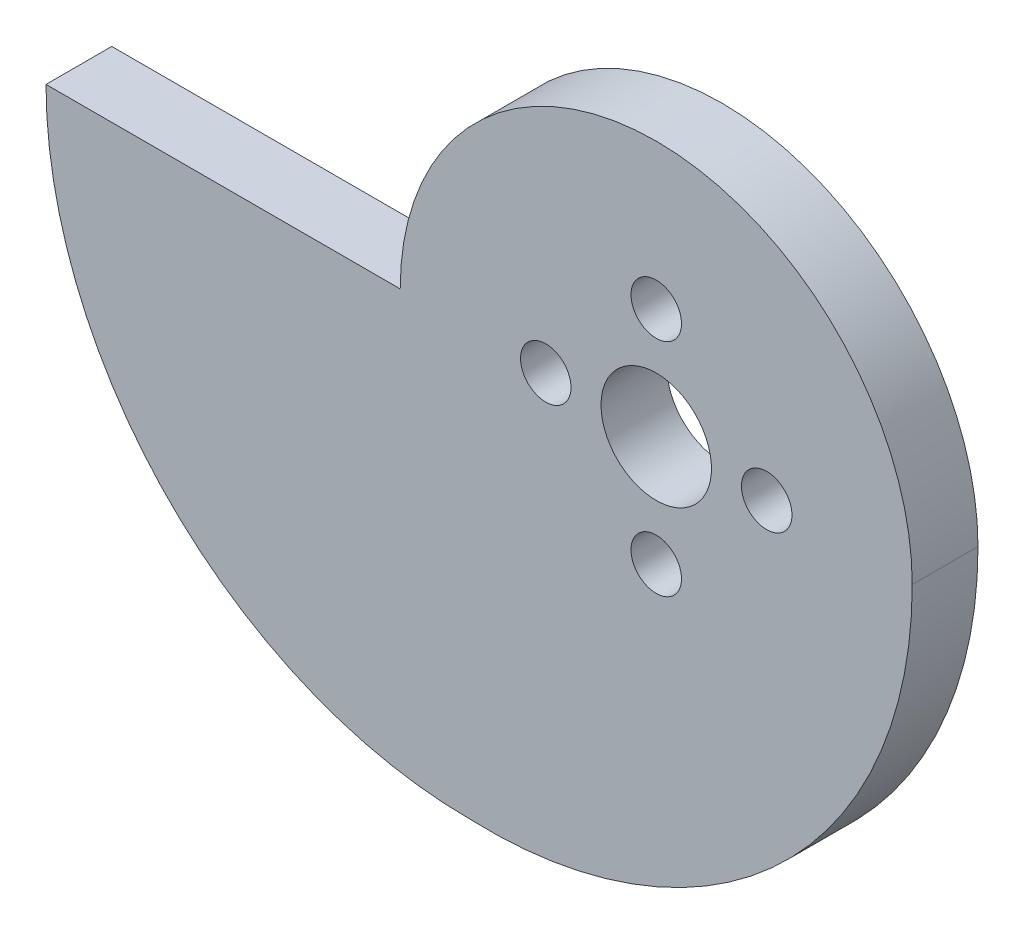
SolidWorks part; units mm, degrees
material "6061-T6 (SS)"
ref_plane "Front" through (0, 0, 0) normal (0, 0, 1) x (1, 0, 0)
ref_plane "Top" through (0, 0, 0) normal (0, 1, 0) x (1, 0, 0)
ref_plane "Right" through (0, 0, 0) normal (1, 0, 0) x (0, 0, -1)
ref_axis "side-side" through (80.9, 0, 0) along (-1, 0, 0)
ref_axis "up-down" through (0, 50, 0) along (0, -1, 0)
ref_axis "front-back" through (0, 0, -80.9) along (0, 0, 1)
sketch3d "3DSketch1"
  circle A4 centre (-8, 0, -7.9375) radius 1.2802
  circle A5 centre (0, -8, -7.9375) radius 1.2802
  circle A6 centre (0, 8, -7.9375) radius 1.2802
  circle A7 centre (8, 0, -7.9375) radius 1.2802
  circle A9 centre (0, 0, 2.5) radius 4
  point P13 (-8, 0, -6.6573)
  point P15 (0, -8, -6.6573)
  point P17 (0, 8, -6.6573)
  point P19 (8, 0, -6.6573)
  point P24 (0, 0, -1.5)
sketch "Sketch1" plane through (0, 0, 0) normal (0, 0, 1) x (1, 0, 0)
  line L0 (-13.462, -30.734) -> (18.542, -30.734) construction
  line L1 (18.542, 17.6106) -> (18.542, -21.2159) construction
  line L2 (50, 0) -> (-50, 0) construction
  line L3 (-44.196, 0) -> (-18.542, 0)
  arc A0 (-18.542, 0) -> (18.542, 0) centre (0, 0) cw
  arc A1 (-44.196, 0) -> (-13.462, -30.734) centre (-13.462, 0) ccw
  arc A2 (18.542, 0) -> (-13.462, -30.734) centre (-12.2172, 0) cw
  circle A3 centre (0, 0) radius 4 construction
  circle A4 centre (0, 0) radius 4
  dimension "D1" = 37.084
  dimension "D2" = 30.734
  dimension "D3" = 62.738
extrude "Boss-Extrude1" add sketch "Sketch1" along normal blind 4.7625
hole_wizard "#6 Clearance Hole1" positions "Sketch2" profile "Sketch3" hole size "#6" standard "ANSI Inch" end condition through all
sketch "Sketch2" plane through (0, 0, 4.7625) normal (0, 0, 1) x (1, 0, 0)
  point P0 (0, 8)
  point P3 (8, 0)
  point P6 (0, -8)
  point P9 (-8, 0)
sketch "Sketch3" plane through (0, 8, 4.7625) normal (1, 0, 0) x (0, -1, 0)
  line L0 (0, 0) -> (0, 4.7625)
  line L1 (0, 4.7625) -> (1.8288, 4.7625)
  line L2 (1.8288, 4.7625) -> (1.8288, 0)
  line L5 (1.8288, 0) -> (0, 0)
  line L11 (0, -6.35) -> (0, 107.95) construction
  dimension "Thru Hole Dia." = 3.6576
  dimension "Thru Hole Depth" = 4.7625
